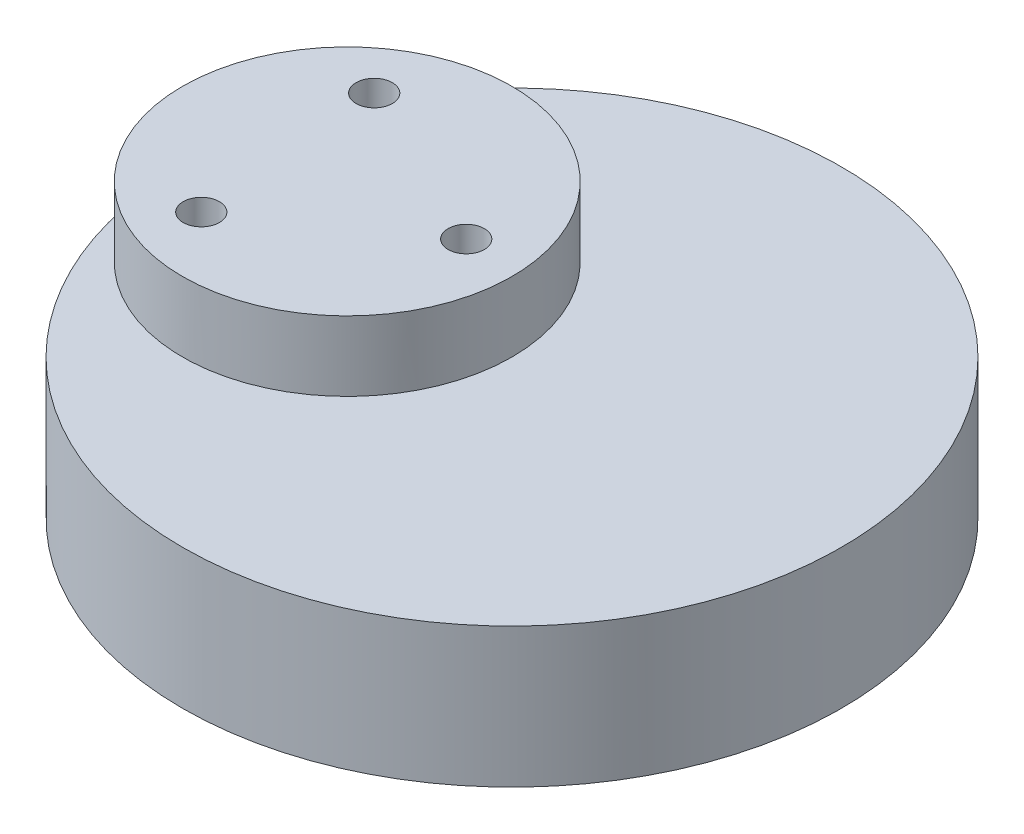
SolidWorks part; units mm, degrees
material "AISI 304"
ref_plane "Front Plane" through (0, 0, 0) normal (0, 0, 1) x (1, 0, 0)
ref_plane "Top Plane" through (0, 0, 0) normal (0, 1, 0) x (1, 0, 0)
ref_plane "Right Plane" through (0, 0, 0) normal (1, 0, 0) x (0, 0, -1)
sketch "Sketch2" plane through (0, 0, 0) normal (0, 1, 0) x (1, 0, 0)
  circle A0 centre (0, 0) radius 15
  circle A1 centre (15, 0) radius 30
  point P5 (0, 0)
  dimension "D1" = 30
  dimension "D2" = 60
  dimension "D3" = 15
extrude "Boss-Extrude1" add sketch "Sketch2" along normal blind 6.35 contours A0 region at (0, 0, 0)
extrude "Boss-Extrude2" add sketch "Sketch2<3>" against normal blind 12.7 contours A0 A1 | A0 region at (0, 0, 0) region at (20, 0, 0)
sketch "Sketch2<3>" plane through (0, 0, 0) normal (0, 1, 0) x (1, 0, 0) same geometry as "Sketch2"
hole_wizard "M4x0.7 Tapped Hole1" positions "Sketch3" profile "Sketch4" tap size "M4x0.7" standard "ANSI Metric"
sketch "Sketch3" plane through (0, 6.35, 0) normal (0, 1, 0) x (1, 0, 0)
  line L0 (-4.2262, -9.0631) -> (0, 0) construction
  line L1 (0, 0) -> (9.9619, 0.8716) construction
  line L3 (-5.7358, 8.1915) -> (0, 0) construction
  line L4 (0, -15) -> (0, 15) construction
  circle A0 centre (0, 0) radius 15 construction
  circle A1 centre (0, 0) radius 15 construction
  point P1 (-4.2262, -9.0631)
  point P5 (9.9619, 0.8716)
  point P7 (-5.7358, 8.1915)
  point P85 (0, 0)
  point P86 (0, -15)
  dimension "D1" = 120
  dimension "D2" = 120
  dimension "D3" = 10
  dimension "D4" = 25
sketch "Sketch4" plane through (-4.2262, 6.35, 9.0631) normal (1, 0, 0) x (0, 0, 1)
  line L0 (0, 0) -> (0, 11.0914)
  line L1 (0, 11.0914) -> (1.65, 10.1)
  line L2 (1.65, 10.1) -> (1.65, 0)
  line L5 (1.65, 0) -> (0, 0)
  line L10 (0, 11.0914) -> (-1.65, 10.1) construction
  line L11 (0, -6.35) -> (0, 107.95) construction
  dimension "Tap Drill Dia." = 3.3
  dimension "Tap Drill Depth" = 10.1
  dimension "Drill Angle" = 118
cosmetic thread "Hole Thread1"
cosmetic thread "Hole Thread2"
cosmetic thread "Hole Thread3"
hole_wizard "M4x0.7 Tapped Hole3" positions "Sketch5" profile "Sketch6" tap size "M4x0.7" standard "ANSI Metric"
sketch "Sketch5" plane through (0, -12.7, 0) normal (0, -1, 0) x (-1, 0, 0)
  line L0 (-15, -20) -> (-15, 0) construction
  line L1 (-15, 0) -> (2.3205, 10) construction
  line L3 (-32.3205, 10) -> (-15, 0) construction
  point P1 (-15, -20)
  point P5 (2.3205, 10)
  point P7 (-32.3205, 10)
  dimension "D1" = 120
  dimension "D2" = 120
  dimension "D3" = 20
sketch "Sketch6" plane through (15, -12.7, 20) normal (1, 0, 0) x (0, 0, -1)
  line L0 (0, 0) -> (0, 11.0914)
  line L1 (0, 11.0914) -> (1.65, 10.1)
  line L2 (1.65, 10.1) -> (1.65, 0)
  line L5 (1.65, 0) -> (0, 0)
  line L10 (0, 11.0914) -> (-1.65, 10.1) construction
  line L11 (0, -6.35) -> (0, 107.95) construction
  dimension "Tap Drill Dia." = 3.3
  dimension "Tap Drill Depth" = 10.1
  dimension "Drill Angle" = 118
cosmetic thread "Hole Thread4"
cosmetic thread "Hole Thread5"
cosmetic thread "Hole Thread6"
